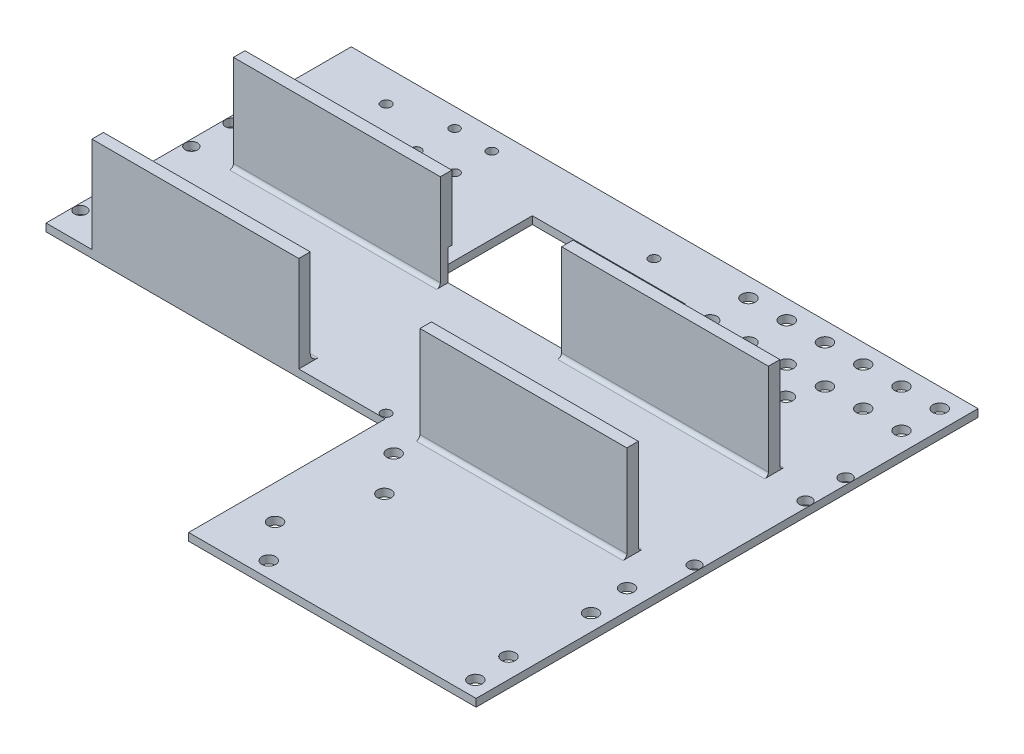
SolidWorks part; units mm, degrees
ref_plane "前视基准面" through (0, 0, 0) normal (0, 0, 1) x (1, 0, 0)
ref_plane "上视基准面" through (0, 0, 0) normal (0, 1, 0) x (1, 0, 0)
ref_plane "右视基准面" through (0, 0, 0) normal (1, 0, 0) x (0, 0, -1)
sketch "草图3" plane through (0, 0, 0) normal (0, 1, 0) x (1, 0, 0)
  line L1 (-81.9007, -43.8513) -> (81.9007, -43.8513)
  line L2 (-81.9007, -43.8513) -> (-81.9007, 43.8513)
  line L3 (-81.9007, 43.8513) -> (81.9007, 43.8513)
  line L4 (81.9007, -43.8513) -> (81.9007, 43.8513)
  line L5 (-81.9007, -43.8513) -> (81.9007, 43.8513) construction
  line L6 (-81.9007, 43.8513) -> (81.9007, -43.8513) construction
  point P0 (0, 0)
extrude "凸台-拉伸1" add sketch "草图3" along normal blind 2 contours L2 L3 L4 L1
sketch "草图4" plane through (0, 0, 0) normal (0, -1, 0) x (1, 0, 0)
  line L0 (-81.9007, -43.8513) -> (81.9007, -43.8513) construction
  line L1 (20, -43.8513) -> (-20, -43.8513)
  line L2 (20, -43.8513) -> (20, -33.8513)
  line L3 (20, -33.8513) -> (-20, -33.8513)
  line L4 (-20, -43.8513) -> (-20, -33.8513)
  line L5 (0, 0) -> (0, 51.7024) construction
  dimension "D1" = 10
  dimension "D2" = 40
extrude "切除-拉伸1" cut sketch "草图4" against normal blind 10
sketch "草图5" plane through (0, 2, 0) normal (0, 1, 0) x (1, 0, 0)
  line L0 (22, 14.8388) -> (63.6813, 14.8388) construction
  line L1 (69.9007, -2.1612) -> (15.8414, -2.1612)
  line L2 (69.9007, -2.1612) -> (69.9007, -5.1612)
  line L3 (69.9007, -5.1612) -> (15.8414, -5.1612)
  line L4 (15.8414, -2.1612) -> (15.8414, -5.1612)
  line L5 (22, 28.8388) -> (22, 0.8388) construction
  line L6 (15.8414, 31.8388) -> (15.8414, 34.8388)
  line L7 (69.9007, 34.8388) -> (15.8414, 34.8388)
  line L8 (69.9007, 31.8388) -> (69.9007, 34.8388)
  line L9 (69.9007, 31.8388) -> (15.8414, 31.8388)
  line L10 (22, 0.8388) -> (31.25, 0.8388) construction
  line L11 (81.9007, -43.8513) -> (81.9007, 43.8513) construction
  line L12 (0, 0) -> (0, 63.1553) construction
  line L13 (-15.8414, -2.1612) -> (-15.8414, -5.1612)
  line L14 (-69.9007, -5.1612) -> (-15.8414, -5.1612)
  line L15 (-69.9007, -2.1612) -> (-69.9007, -5.1612)
  line L16 (-69.9007, -2.1612) -> (-15.8414, -2.1612)
  line L17 (-69.9007, 31.8388) -> (-15.8414, 31.8388)
  line L18 (-69.9007, 31.8388) -> (-69.9007, 34.8388)
  line L19 (-69.9007, 34.8388) -> (-15.8414, 34.8388)
  line L20 (-15.8414, 31.8388) -> (-15.8414, 34.8388)
  dimension "D1" = 3
  dimension "D2" = 3
  dimension "D3" = 12
extrude "凸台-拉伸2" add sketch "草图5" along normal blind 25
sketch "草图6" plane through (0, 0, 0) normal (0, -1, 0) x (1, 0, 0)
  line L0 (-81.9007, 43.8513) -> (81.9007, 43.8513) construction
  line L1 (-81.9007, 43.8513) -> (81.9007, 43.8513)
  line L2 (-81.9007, 43.8513) -> (-81.9007, 22.5557)
  line L3 (-81.9007, 22.5557) -> (81.9007, 22.5557)
  line L4 (81.9007, 43.8513) -> (81.9007, 22.5557)
  line L5 (81.9007, 43.8513) -> (81.9007, -43.8513) construction
extrude "切除-拉伸2" cut sketch "草图6" against normal through all
sketch "草图7" plane through (0, 0, 0) normal (0, -1, 0) x (1, 0, 0)
  line L1 (-81.9007, 22.5557) -> (-9.1726, 22.5557)
  line L2 (-81.9007, 22.5557) -> (-81.9007, 12.5557)
  line L3 (-81.9007, 12.5557) -> (-9.1726, 12.5557)
  line L4 (-9.1726, 22.5557) -> (-9.1726, 12.5557)
  dimension "D1" = 10
extrude "切除-拉伸3" cut sketch "草图7" against normal through all
sketch "草图8" plane through (0, 2, 0) normal (0, 1, 0) x (1, 0, 0)
  line L0 (20, 34.8388) -> (20, 43.8513) construction
  line L1 (-81.9007, 43.8513) -> (-20, 43.8513)
  line L2 (-81.9007, 43.8513) -> (-81.9007, 80.8107)
  line L3 (-81.9007, 80.8107) -> (-20, 80.8107)
  line L4 (-20, 43.8513) -> (-20, 80.8107)
  line L5 (81.9007, 43.8513) -> (20, 43.8513)
  line L6 (81.9007, 43.8513) -> (81.9007, 82.4667)
  line L7 (81.9007, 82.4667) -> (20, 82.4667)
  line L8 (20, 43.8513) -> (20, 82.4667)
  line L9 (-20, 43.8513) -> (-20, 34.8388) construction
extrude "凸台-拉伸3" add sketch "草图8" against normal up to surface (2 mm away) up to face at (-1.8345, 0, -17.2885)
sketch "草图9" plane through (0, 2, 0) normal (0, 1, 0) x (1, 0, 0)
  line L0 (-9.1726, -22.5557) -> (-9.1726, -12.5557) construction
  line L1 (-81.9007, -12.5557) -> (-9.1726, -12.5557)
  line L2 (-81.9007, -12.5557) -> (-81.9007, -5.1612)
  line L3 (-81.9007, -5.1612) -> (-9.1726, -5.1612)
  line L4 (-9.1726, -12.5557) -> (-9.1726, -5.1612)
  line L5 (-69.9007, -5.1612) -> (-15.8414, -5.1612) construction
extrude "切除-拉伸4" cut sketch "草图9" against normal blind 10
sketch "草图10" plane through (0, 2, 0) normal (0, 1, 0) x (1, 0, 0)
  circle A0 centre (80.25, 41.6796) radius 1.6
  circle A1 centre (80.25, 31.1796) radius 1.6
  circle A2 centre (80.25, 2.1796) radius 1.6
  circle A3 centre (-80.25, 41.6796) radius 1.6
  circle A4 centre (-80.25, 31.1796) radius 1.6
  circle A5 centre (-80.25, 2.1796) radius 1.6
  dimension "D1" = 3.2
extrude "切除-拉伸5" cut sketch "草图10" against normal blind 10
sketch "草图12" plane through (0, 0, 0) normal (0, -1, 0) x (1, 0, 0)
  line L0 (-9.1726, 22.5557) -> (81.9007, 22.5557) construction
  line L1 (-9.1726, 5.1612) -> (6.7765, 5.1612)
  line L2 (-9.1726, 5.1612) -> (-9.1726, 22.5557)
  line L3 (-9.1726, 22.5557) -> (6.7765, 22.5557)
  line L4 (6.7765, 5.1612) -> (6.7765, 22.5557)
extrude "切除-拉伸6" cut sketch "草图12" against normal blind 10
sketch "草图13" plane through (0, 0, 0) normal (0, -1, 0) x (1, 0, 0)
  line L0 (81.9007, 22.5557) -> (81.9007, -82.4667) construction
  line L5 (81.9007, -74.6223) -> (-85.7635, -74.6223)
  line L6 (81.9007, -74.6223) -> (81.9007, -87.6035)
  line L7 (81.9007, -87.6035) -> (-85.7635, -87.6035)
  line L8 (-85.7635, -74.6223) -> (-85.7635, -87.6035)
extrude "切除-拉伸7" cut sketch "草图13" against normal blind 10
sketch "草图14" plane through (0, 0, 0) normal (0, -1, 0) x (1, 0, 0)
  line L0 (20, -33.8513) -> (-20, -33.8513) construction
  line L1 (20, -74.6223) -> (12, -74.6223)
  line L2 (20, -74.6223) -> (20, -33.8513)
  line L3 (20, -33.8513) -> (12, -33.8513)
  line L4 (12, -74.6223) -> (12, -33.8513)
  line L5 (-20, -33.8513) -> (-20, -74.6223) construction
  dimension "D1" = 32
extrude "凸台-拉伸4" add sketch "草图14" against normal up to surface (2 mm away) up to face at (-7.1787, 2, -25.5829)
sketch "草图15" plane through (0, 0, 0) normal (0, -1, 0) x (1, 0, 0)
  line L0 (12, -33.8513) -> (12, -74.6223) construction
  line L1 (-20, -74.6223) -> (12, -74.6223)
  line L2 (-20, -74.6223) -> (-20, -60.0491)
  line L3 (-20, -60.0491) -> (12, -60.0491)
  line L4 (12, -74.6223) -> (12, -60.0491)
extrude "凸台-拉伸5" add sketch "草图15" against normal up to surface (2 mm away) up to face at (-19.1898, 2, -23.8594)
sketch "草图17" plane through (0, 0, 0) normal (0, -1, 0) x (1, 0, 0)
  line L0 (0, 0) -> (0, -128.7991) construction
  line L2 (-20, -33.8513) -> (20, -33.8513)
  line L3 (-20, -33.8513) -> (-20, -60.0491)
  line L4 (-20, -60.0491) -> (20, -60.0491)
  line L5 (20, -33.8513) -> (20, -60.0491)
  dimension "D1" = 40
extrude "切除-拉伸8" cut sketch "草图17" against normal blind 10
sketch "草图18" plane through (0, 0, 0) normal (0, -1, 0) x (1, 0, 0)
  circle A0 centre (-64.3876, 3.7726) radius 1.3
  circle A1 centre (-64.3876, -66.2274) radius 1.3
  circle A2 centre (5.6124, -66.2274) radius 1.3
  circle A3 centre (5.6124, 3.7726) radius 1.3
  dimension "D1" = 2.6
extrude "切除-拉伸9" cut sketch "草图18" against normal blind 10
sketch "草图19" plane through (0, 0, 0) normal (0, -1, 0) x (1, 0, 0)
  line L0 (81.9007, 22.5557) -> (81.9007, -74.6223) construction
  line L1 (6.7765, 22.5557) -> (81.9007, 22.5557)
  line L2 (6.7765, 22.5557) -> (6.7765, 56.5557)
  line L3 (6.7765, 56.5557) -> (81.9007, 56.5557)
  line L4 (81.9007, 22.5557) -> (81.9007, 56.5557)
  dimension "D1" = 34
extrude "凸台-拉伸7" add sketch "草图19" against normal up to surface (2 mm away) up to face at (5.6124, 2, 5.0726)
hole_wizard "M3 螺纹孔的螺纹孔钻头1" positions "草图21" profile "草图22" hole size "M3" standard "GB"
sketch "草图21" plane through (0, 0, 0) normal (0, -1, 0) x (-1, 0, 0)
  point P0 (-23.8856, -1.8042)
  point P3 (-54.1156, -1.8042)
sketch "草图22" plane through (23.8856, 0, 1.8042) normal (1, 0, 0) x (0, 0, -1)
  line L0 (0, 0) -> (0, 13.1511)
  line L1 (0, 13.1511) -> (1.25, 12.4)
  line L2 (1.25, 12.4) -> (1.25, 0)
  line L5 (1.25, 0) -> (0, 0)
  line L10 (0, 13.1511) -> (-1.25, 12.4) construction
  line L11 (0, -6.35) -> (0, 107.95) construction
  dimension "孔直径" = 2.5
  dimension "孔深度" = 12.4
  dimension "导头角度" = 118
hole_wizard "M3 间隙孔1" positions "草图23" profile "草图24" hole size "M3" standard "GB"
sketch "草图23" plane through (0, 0, 0) normal (0, -1, 0) x (-1, 0, 0)
  point P0 (-23.8856, 52.1958)
  point P3 (-54.1156, 52.1958)
  point P6 (-77.6106, -22.2238)
  point P9 (-23.6106, -22.2238)
  point P12 (-77.6106, -52.4538)
  point P15 (-23.6106, -52.4538)
sketch "草图24" plane through (23.8856, 0, -52.1958) normal (1, 0, 0) x (0, 0, -1)
  line L0 (0, 0) -> (0, 13.4815)
  line L1 (0, 13.4815) -> (1.8, 12.4)
  line L2 (1.8, 12.4) -> (1.8, 0)
  line L5 (1.8, 0) -> (0, 0)
  line L10 (0, 13.4815) -> (-1.8, 12.4) construction
  line L11 (0, -6.35) -> (0, 107.95) construction
  dimension "孔直径" = 3.6
  dimension "孔深度" = 12.4
  dimension "导头角度" = 118
hole_wizard "M3 间隙孔2" positions "草图25" profile "草图26" hole size "M3" standard "GB"
sketch "草图25" plane through (0, 2, 0) normal (0, 1, 0) x (1, 0, 0)
  point P0 (76.6824, -42.8767)
  point P3 (76.6824, -11.8767)
  point P6 (15.6824, -11.8767)
  point P9 (15.6824, -42.8767)
sketch "草图26" plane through (76.6824, 2, 42.8767) normal (1, 0, 0) x (0, 0, 1)
  line L0 (0, 0) -> (0, 13.4815)
  line L1 (0, 13.4815) -> (1.8, 12.4)
  line L2 (1.8, 12.4) -> (1.8, 0)
  line L5 (1.8, 0) -> (0, 0)
  line L10 (0, 13.4815) -> (-1.8, 12.4) construction
  line L11 (0, -6.35) -> (0, 107.95) construction
  dimension "孔直径" = 3.6
  dimension "孔深度" = 12.4
  dimension "导头角度" = 118
hole_wizard "M3 间隙孔3" positions "草图27" profile "草图28" hole size "M3" standard "GB"
sketch "草图27" plane through (0, 0, 0) normal (0, -1, 0) x (-1, 0, 0)
  line L0 (-81.9007, 74.6223) -> (81.9007, 74.6223) construction
  line L1 (-81.9007, -56.5557) -> (-81.9007, 74.6223) construction
  point P0 (-76.9007, 69.6223)
  point P2 (-66.9007, 69.6223)
  point P4 (-76.9007, 59.6223)
  point P28 (-56.9007, 69.6223)
  point P29 (-46.9007, 69.6223)
  point P30 (-36.9007, 69.6223)
  point P31 (-26.9007, 69.6223)
  point P33 (-56.9007, 59.6223)
  point P34 (-46.9007, 59.6223)
  point P35 (-36.9007, 59.6223)
  point P36 (-26.9007, 59.6223)
  point P38 (-66.9007, 59.6223)
  point P39 (-16.9007, 59.6223) [skipped]
  point P40 (-16.9007, 69.6223) [skipped]
  dimension "D1" = 6
  dimension "D2" = 10
  dimension "D3" = 10
  dimension "D4" = 5
  dimension "D5" = 5
  dimension "D7" = 10
  dimension "D8" = 10
  dimension "D6" = 2
sketch "草图28" plane through (76.9007, 0, -69.6223) normal (1, 0, 0) x (0, 0, -1)
  line L0 (0, 0) -> (0, 13.4815)
  line L1 (0, 13.4815) -> (1.8, 12.4)
  line L2 (1.8, 12.4) -> (1.8, 0)
  line L5 (1.8, 0) -> (0, 0)
  line L10 (0, 13.4815) -> (-1.8, 12.4) construction
  line L11 (0, -6.35) -> (0, 107.95) construction
  dimension "孔直径" = 3.6
  dimension "孔深度" = 12.4
  dimension "导头角度" = 118
hole_wizard "M3 螺纹孔的螺纹孔钻头2" positions "草图29" profile "草图30" hole size "M3" standard "GB"
sketch "草图29" plane through (0, 0, 0) normal (0, -1, 0) x (-1, 0, 0)
  line L0 (-81.9007, 74.6223) -> (81.9007, 74.6223) construction
  line L1 (81.9007, -5.1612) -> (81.9007, 74.6223) construction
  point P0 (49.9007, 69.6223)
  point P2 (39.9007, 69.34)
  point P4 (39.9007, 59.6223)
  point P6 (49.9007, 59.6223)
  dimension "D1" = 10
  dimension "D2" = 10
  dimension "D3" = 5
  dimension "D4" = 32
sketch "草图30" plane through (-49.9007, 0, -69.6223) normal (1, 0, 0) x (0, 0, -1)
  line L0 (0, 0) -> (0, 13.1511)
  line L1 (0, 13.1511) -> (1.25, 12.4)
  line L2 (1.25, 12.4) -> (1.25, 0)
  line L5 (1.25, 0) -> (0, 0)
  line L10 (0, 13.1511) -> (-1.25, 12.4) construction
  line L11 (0, -6.35) -> (0, 107.95) construction
  dimension "孔直径" = 2.5
  dimension "孔深度" = 12.4
  dimension "导头角度" = 118
fillet "圆角1" radius 1 5 edges at (42.8711, 2, 5.1612) (42.8711, 2, -31.8388) (44.9504, 2, -34.8388) (-44.9504, 2, -34.8388) (-42.8711, 2, -31.8388)
fillet "圆角2" radius 2 1 edges at (-42.8711, 2, 2.1612)
fillet "圆角3" radius 1 1 edges at (62.6071, 2, 2.1612)
